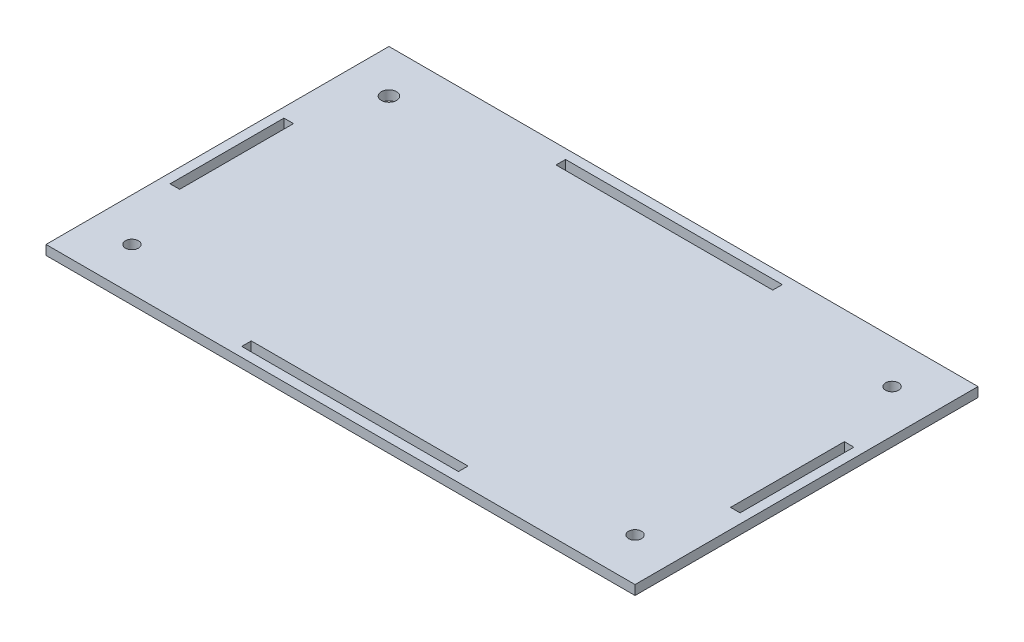
SolidWorks part; units mm, degrees
ref_plane "Front Plane" through (0, 0, 0) normal (0, 0, 1) x (1, 0, 0)
ref_plane "Top Plane" through (0, 0, 0) normal (0, 1, 0) x (1, 0, 0)
ref_plane "Right Plane" through (0, 0, 0) normal (1, 0, 0) x (0, 0, -1)
sketch "Sketch2" plane through (0, 0, 0) normal (0, 1, 0) x (1, 0, 0)
  line L15 (-5.2235, 66.6261) -> (118.1865, 66.6261)
  line L16 (-5.2235, 66.6261) -> (-5.2235, -5.2219)
  line L17 (-5.2235, -5.2219) -> (118.1865, -5.2219)
  line L18 (118.1865, 66.6261) -> (118.1865, -5.2219)
  line L19 (-1.2235, 42.6261) -> (-3.2235, 42.6261)
  line L20 (-1.2235, 42.6261) -> (-1.2235, 18.7781)
  line L21 (-1.2235, 18.7781) -> (-3.2235, 18.7781)
  line L22 (-3.2235, 42.6261) -> (-3.2235, 18.7781)
  line L23 (33.7765, 62.6261) -> (79.1865, 62.6261)
  line L24 (33.7765, 62.6261) -> (33.7765, 64.6261)
  line L25 (33.7765, 64.6261) -> (79.1865, 64.6261)
  line L26 (79.1865, 62.6261) -> (79.1865, 64.6261)
  line L27 (114.1865, 42.6261) -> (116.1865, 42.6261)
  line L28 (114.1865, 42.6261) -> (114.1865, 18.7781)
  line L29 (114.1865, 18.7781) -> (116.1865, 18.7781)
  line L30 (116.1865, 42.6261) -> (116.1865, 18.7781)
  line L31 (79.1865, -1.2219) -> (33.7765, -1.2219)
  line L32 (79.1865, -1.2219) -> (79.1865, -3.2219)
  line L33 (79.1865, -3.2219) -> (33.7765, -3.2219)
  line L34 (33.7765, -1.2219) -> (33.7765, -3.2219)
  circle A0 centre (3.7765, 3.7781) radius 1.3609
  circle A1 centre (109.1865, 3.7781) radius 1.3609
  circle A2 centre (3.7765, 57.6261) radius 1.6
  circle A3 centre (109.1865, 57.6261) radius 1.3609
  point P34 (33.7765, -2.2219)
  point P35 (115.1865, 42.6261)
  dimension "D1" = 105.41
  dimension "D2" = 53.848
  dimension "D3" = 15
  dimension "D4" = 15
  dimension "D5" = 30
  dimension "D6" = 30
  dimension "D7" = 30
  dimension "D8" = 30
  dimension "D9" = 15
  dimension "D10" = 15
  dimension "D11" = 5
  dimension "D12" = 2
  dimension "D13" = 5
  dimension "D14" = 5
  dimension "D15" = 5
  dimension "D16" = 9
  dimension "D17" = 9
  dimension "D18" = 9
  dimension "D19" = 9
extrude "Boss-Extrude1" add sketch "Sketch2" along normal blind 2
